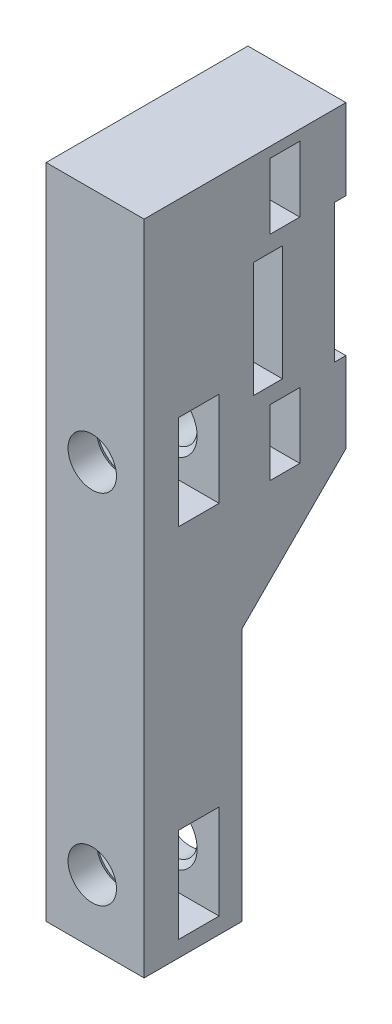
SolidWorks part; units mm, degrees
ref_plane "Plan de face" through (0, 0, 0) normal (0, 0, 1) x (1, 0, 0)
ref_plane "Plan de dessus" through (0, 0, 0) normal (0, 1, 0) x (1, 0, 0)
ref_plane "Plan de droite" through (0, 0, 0) normal (1, 0, 0) x (0, 0, -1)
sketch "Esquisse1" plane through (0, 0, 0) normal (0, 0, 1) x (1, 0, 0)
  line L0 (4, 51.5) -> (4, 20.5) construction
  line L1 (0, 0) -> (8.5, 0)
  line L2 (0, 0) -> (0, 72)
  line L3 (0, 72) -> (8.5, 72)
  line L4 (8.5, 0) -> (8.5, 72)
  circle A0 centre (4, 20.5) radius 2.1
  circle A1 centre (4, 51.5) radius 2.1
  point P9 (4, 36)
  point P10 (0, 36)
  dimension "D1" = 4.2
  dimension "D2" = 4.2
  dimension "D3" = 31
  dimension "D4" = 72
  dimension "D6" = 8.5
  dimension "D8" = 4
extrude "Boss.-Extru.1" add sketch "Esquisse1" along normal blind 17.5
sketch "Esquisse6" plane through (0, 0, 17.5) normal (0, 0, 1) x (1, 0, 0)
  line L0 (8.5, 0) -> (8.5, 72) construction
  line L1 (4, 24.5992) -> (0.45, 22.5496)
  line L2 (0.45, 22.5496) -> (0.45, 18.4504)
  line L3 (0.45, 18.4504) -> (4, 16.4008)
  line L4 (4, 16.4008) -> (7.55, 18.4504)
  line L5 (7.55, 18.4504) -> (7.55, 22.5496)
  line L6 (7.55, 22.5496) -> (4, 24.5992)
  line L7 (4, 16.4008) -> (8.5, 16.4008)
  line L8 (8.5, 16.4008) -> (8.5, 24.5992)
  line L9 (8.5, 24.5992) -> (4, 24.5992)
  circle A0 centre (4, 20.5) radius 3.55 construction
  line M9 (8.5, 0) -> (8.5, 72)
  circle M11 centre (4, 20.5) radius 2.1
  dimension "D1" = 7.1
extrude "Enlèv. mat.-Extru.4" cut sketch "Esquisse6" against normal blind 3.5 from offset 3 contours L9 L6 L5 L4 M9 | L5 L6 L1 L2 L3 L4 M11 region at (5.7208, 23.4805, 17.5) region at (6.25, 24.5057, 17.5) offset against normal yes
sketch "Esquisse7" plane through (0, 0, 0) normal (0, 0, -1) x (-1, 0, 0)
  circle A0 centre (-4, 20.5) radius 2.1
extrude "Boss.-Extru.3" add sketch "Esquisse7" against normal blind 7
sketch "Esquisse3" plane through (0, 0, 0) normal (0, -1, 0) x (-1, 0, 0)
  line L0 (-8.5, -17.5) -> (-8.5, 0) construction
  line L1 (0, 0) -> (-8.5, 0)
  line L2 (0, 0) -> (0, -4)
  line L3 (0, -4) -> (-8.5, -4)
  line L4 (-8.5, 0) -> (-8.5, -4)
  dimension "D1" = 4
extrude "Enlèv. mat.-Extru.3" cut sketch "Esquisse3" against normal blind 19
sketch "Esquisse5" plane through (0, 0, 0) normal (0, -1, 0) x (1, 0, 0)
  line L0 (8.5, 1) -> (0, 1)
  line L1 (8.5, 4) -> (0, 4)
  line L2 (8.5, 4) -> (8.5, 0.75)
  line L3 (8.5, 0.75) -> (0, 0.75)
  line L4 (0, 4) -> (0, 0.75)
  line L5 (8.5, 1.75) -> (0, 1.75)
  line L6 (4.85, 1) -> (4.85, 1.277)
  line L7 (5.65, 1) -> (5.65, 1.277)
  line L8 (0, 0) -> (8.5, 0) construction
  circle A0 centre (5.25, 1.195) radius 0.555
  arc A1 (5.7174, 1.4942) -> (5.8483, 1) centre (4.85, 1) cw
  arc A2 (4.8056, 1.5275) -> (4.6544, 1) centre (5.65, 1) ccw
  circle A3 centre (4.5143, 1.15) radius 0.15
  circle A4 centre (5.9885, 1.15) radius 0.15
  circle A5 centre (7.25, 1.195) radius 0.555
  arc A6 (7.7174, 1.4942) -> (7.8483, 1) centre (6.85, 1) cw
  circle A7 centre (7.9885, 1.15) radius 0.15
  circle A8 centre (6.5143, 1.15) radius 0.15
  arc A9 (6.8056, 1.5275) -> (6.6544, 1) centre (7.65, 1) ccw
  circle A10 centre (3.25, 1.195) radius 0.555
  arc A11 (3.7174, 1.4942) -> (3.8483, 1) centre (2.85, 1) cw
  circle A12 centre (3.9885, 1.15) radius 0.15
  circle A13 centre (2.5143, 1.15) radius 0.15
  arc A14 (2.8056, 1.5275) -> (2.6544, 1) centre (3.65, 1) ccw
  circle A15 centre (1.25, 1.195) radius 0.555
  arc A16 (1.7174, 1.4942) -> (1.8483, 1) centre (0.85, 1) cw
  circle A17 centre (1.9885, 1.15) radius 0.15
  circle A18 centre (0.5143, 1.15) radius 0.15
  arc A19 (0.8056, 1.5275) -> (0.6544, 1) centre (1.65, 1) ccw
  circle A20 centre (-0.75, 1.195) radius 0.555
  arc A21 (-0.2826, 1.4942) -> (-0.1517, 1) centre (-1.15, 1) cw
  circle A22 centre (-0.0115, 1.15) radius 0.15
  circle A23 centre (-1.4857, 1.15) radius 0.15
  arc A24 (-1.1944, 1.5275) -> (-1.3456, 1) centre (-0.35, 1) ccw
  circle A25 centre (9.25, 1.195) radius 0.555
  circle A26 centre (8.5143, 1.15) radius 0.15
  arc A27 (8.8056, 1.5275) -> (8.6544, 1) centre (9.65, 1) ccw
  arc A28 (9.7174, 1.4942) -> (9.8483, 1) centre (8.85, 1) cw
  circle A29 centre (9.9885, 1.15) radius 0.15
  point P9 (4.25, 1)
  point P16 (4.85, 1.1385)
  line M16 (0, 4) -> (8.5, 4)
  dimension "D2" = 1.11
  dimension "D7" = 0.3
  dimension "D8" = 0.3
  dimension "D1" = 1
  dimension "D3" = 0.75
  dimension "D4" = 0.25
  dimension "D5" = 0.4
  dimension "D6" = 0.4
  dimension "D12" = 1
  dimension "D9" = 2
  dimension "D10" = 4
  dimension "D11" = 2
extrude "Boss.-Extru.2" add sketch "Esquisse5" against normal blind 12 from offset 7 contours A26 L2 L5 A5 A6 A7 L0 | A9 A5 L5 A0 A1 A4 L0 A8 | A12 L0 A3 A2 A0 L5 A10 A11 | A17 L0 A13 A14 A10 L5 A15 A16 | A22 L4 L0 A18 A19 A15 L5 | A18 | L4 A22 | L2 A26 | A7 | A8 | A4 | A3 | A12 | L5 L2 L4 M16 | A17 | A13 region at (4.2503, 0, 1.4888) region at (6.2503, 0, 1.4888) region at (5.9885, 0, 1.15) region at (4.5143, 0, 1.15) region at (6.5143, 0, 1.15) region at (3.9885, 0, 1.15) region at (4.25, 0, 2.875) region at (8.1006, 0, 1.4663) region at (2.2503, 0, 1.4888) region at (0.4001, 0, 1.4662) region at (7.9885, 0, 1.15) region at (8.4428, 0, 1.15) region at (2.5143, 0, 1.15) region at (0.0584, 0, 1.15) region at (1.9885, 0, 1.15) region at (0.5143, 0, 1.15) offset against normal yes
sketch "Esquisse8" plane through (0, 0, 4) normal (0, 0, -1) x (-1, 0, 0)
  line L0 (-8.5, 7) -> (-8.5, 0) construction
  line L1 (0, 0) -> (-8.5, 0)
  line L2 (0, 0) -> (0, 7)
  line L3 (0, 7) -> (-8.5, 7)
  line L4 (-8.5, 0) -> (-8.5, 7)
  line L5 (0, 7) -> (-8.5, 7) construction
extrude "Boss.-Extru.4" add sketch "Esquisse8" along normal up to surface (4 mm away) up to face at (4.25, 45.5, 0)
sketch "Esquisse9" plane through (0, 0, 0) normal (0, 0, -1) x (-1, 0, 0)
  line L0 (-8.5, 0) -> (0, 0) construction
  line L1 (0, 7) -> (-8.5, 7) construction
  line L2 (0, 19) -> (-8.5, 19) construction
  circle A0 centre (-4.25, 3.75) radius 1.6
  circle A1 centre (-4.25, 22.25) radius 1.6
  point P7 (-4.25, 0)
  dimension "D1" = 3.2
  dimension "D2" = 3.2
  dimension "D3" = 3.25
  dimension "D4" = 3.25
extrude "Enlèv. mat.-Extru.5" cut sketch "Esquisse9" against normal blind 5
sketch "Esquisse10" plane through (0, 0, 0) normal (0, 0, -1) x (-1, 0, 0)
  line L0 (-5.8954, 25.1) -> (-8.5, 25.1)
  line L1 (-7.5409, 22.25) -> (-5.8954, 19.4)
  line L2 (-5.8954, 19.4) -> (-2.6046, 19.4)
  line L3 (-2.6046, 19.4) -> (-0.9591, 22.25)
  line L4 (-0.9591, 22.25) -> (-2.6046, 25.1)
  line L5 (-2.6046, 25.1) -> (-5.8954, 25.1)
  line L6 (-5.8954, 25.1) -> (-7.5409, 22.25)
  line L7 (-7.5409, 3.75) -> (-5.8954, 0.9)
  line L8 (-5.8954, 0.9) -> (-2.6046, 0.9)
  line L9 (-2.6046, 0.9) -> (-0.9591, 3.75)
  line L10 (-0.9591, 3.75) -> (-2.6046, 6.6)
  line L11 (-2.6046, 6.6) -> (-5.8954, 6.6)
  line L12 (-5.8954, 6.6) -> (-7.5409, 3.75)
  line L13 (-8.5, 19) -> (-8.5, 72) construction
  line L14 (-5.8954, 19.4) -> (-8.5, 19.4)
  line L15 (-8.5, 19.4) -> (-8.5, 25.1)
  line L16 (-5.8954, 0.9) -> (-8.5, 0.9)
  line L17 (-8.5, 0.9) -> (-8.5, 6.6)
  line L18 (-8.5, 19) -> (-8.5, 7) construction
  line L19 (-8.5, 6.6) -> (-5.8954, 6.6)
  circle A0 centre (-4.25, 22.25) radius 2.85 construction
  circle A1 centre (-4.25, 3.75) radius 2.85 construction
  circle M5 centre (-4.25, 22.25) radius 1.6
  line M9 (-8.5, 72) -> (-8.5, 19)
  dimension "D1" = 5.7
  dimension "D2" = 5.7
extrude "Enlèv. mat.-Extru.6" cut sketch "Esquisse10" against normal blind 2.6 from offset 4 contours L5 L6 L1 L2 L3 L4 M5 | L11 L12 L7 L8 L9 L10 | L19 L17 L16 L7 L12 | L14 L1 L6 L0 M9 region at (7.5458, 22.25, 0) region at (4.25, 25.0129, 0) region at (4.25, 3.75, 0) region at (7.5458, 3.75, 0) offset against normal yes
sketch "Esquisse11" plane through (0, 0, 5) normal (0, 0, -1) x (-1, 0, 0)
  circle A0 centre (-4.25, 22.25) radius 1.6
  circle A1 centre (-4.25, 22.25) radius 1.6 construction
extrude "Enlèv. mat.-Extru.7" cut sketch "Esquisse11" against normal up to surface (1.6 mm away) up to face at (2.65, 22.25, 6.6)
sketch "Esquisse14" plane through (8.5, 0, 0) normal (1, 0, 0) x (0, 0, -1)
  line L1 (-8, 18) -> (-5.5, 18)
  line L2 (-8, 18) -> (-8, 8)
  line L3 (-8, 8) -> (-5.5, 8)
  line L4 (-5.5, 18) -> (-5.5, 8)
  line L6 (-17.5, 0) -> (-17.5, 72) construction
  line L8 (0, 19) -> (-1, 19) construction
  dimension "D1" = 2.5
  dimension "D2" = 9.5
  dimension "D3" = 10
  dimension "D4" = 1
extrude "Enlèv. mat.-Extru.9" cut sketch "Esquisse14" against normal blind 17.6
ref_plane "Plan1" through (0, 36, 0) normal (0, -1, 0) x (-1, 0, 0)
mirror "Symétrie14" about plane through (0, 36, 0) normal (0, -1, 0) of "Enlèv. mat.-Extru.9", "Enlèv. mat.-Extru.4", "Boss.-Extru.3", "Enlèv. mat.-Extru.3", "Boss.-Extru.2", "Boss.-Extru.4", "Enlèv. mat.-Extru.5", "Enlèv. mat.-Extru.6", "Enlèv. mat.-Extru.7"
chamfer "Chanfrein1" distance 0.5 angle 45 4 edges at (6.1, 20.5, 11) (6.1, 20.5, 14.5) (6.1, 51.5, 14.5) (6.1, 51.5, 11)
sketch "Esquisse15" plane through (8.5, 0, 0) normal (1, 0, 0) x (0, 0, -1)
  line L0 (-17.5, 72) -> (0, 72) construction
  line L1 (0, 0) -> (-9, 0)
  line L2 (0, 0) -> (0, 46)
  line L3 (0, 46) -> (-9, 46)
  line L4 (-9, 0) -> (-9, 46)
  line L5 (-9, 15) -> (-17.5, 15)
  line L6 (-17.5, 0) -> (-17.5, 72) construction
  line L7 (-17.5, 0) -> (0, 0) construction
  line M8 (-6.6, 19.4) -> (-6.6, 25.1)
  line M9 (-6.6, 25.1) -> (-4, 25.1)
  line M10 (-4, 25.1) -> (-4, 19.4)
  line M11 (-4, 19.4) -> (-6.6, 19.4)
  line M16 (-6.6, 0.9) -> (-6.6, 6.6)
  line M17 (-6.6, 6.6) -> (-4, 6.6)
  line M18 (-4, 6.6) -> (-4, 0.9)
  line M19 (-4, 0.9) -> (-6.6, 0.9)
  line M20 (-5.5, 8) -> (-8, 8)
  line M21 (-8, 8) -> (-8, 18)
  line M22 (-8, 18) -> (-5.5, 18)
  line M23 (-5.5, 18) -> (-5.5, 8)
  line M30 (-17.5, 72) -> (-17.5, 0)
  line M31 (-17.5, 0) -> (0, 0)
  line M32 (0, 0) -> (0, 7)
  line M33 (0, 7) -> (-1, 7)
  line M34 (-1, 7) -> (-1, 19)
  line M35 (-1, 19) -> (0, 19)
  line M36 (0, 19) -> (0, 53)
  dimension "D1" = 9
  dimension "D2" = 26
  dimension "D3" = 15
extrude "Enlèv. mat.-Extru.10" cut sketch "Esquisse15" against normal blind 10 contours L4 L5 M30 M31 | L4 L3 M31 M32 M33 M34 M35 M36 M23 M20 M21 M22 M19 M16 M17 M18 M11 M8 M9 M10 region at (8.5, 0.4687, 4.5) region at (8.5, 7.5, 13.25) body kept at (6.6, 20.5, 11)
chamfer "Chanfrein2" distance 9 angle 45 1 edges at (4.25, 46, 9)
